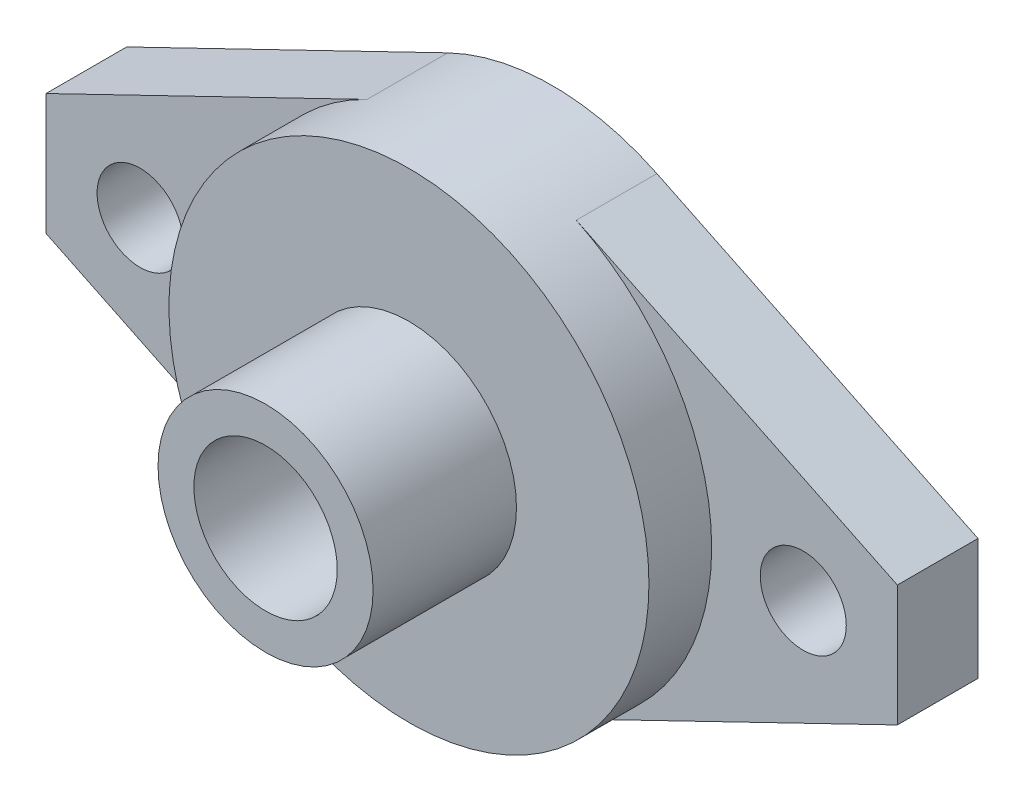
SolidWorks part; units mm, degrees
ref_plane "前视基准面" through (0, 0, 0) normal (0, 0, 1) x (1, 0, 0)
ref_plane "上视基准面" through (0, 0, 0) normal (0, 1, 0) x (1, 0, 0)
ref_plane "右视基准面" through (0, 0, 0) normal (1, 0, 0) x (0, 0, -1)
sketch "草图1" plane through (0, 0, 0) normal (0, 0, 1) x (1, 0, 0)
  line L0 (23.75, -3.3807) -> (23.75, 3.3807)
  line L1 (0, -13.3911) -> (0, -13.25) construction
  line L2 (-23.75, -3.3807) -> (-23.75, 3.3807)
  line L3 (23.75, 3.3807) -> (5.8347, 12.0531)
  line L4 (-23.75, 3.3807) -> (-5.8347, 12.0531)
  line L5 (-23.75, -3.3807) -> (-5.6321, -12.1512)
  line L6 (23.75, -3.3807) -> (5.6321, -12.1512)
  line L8 (0, 13.25) -> (0, 13.3911) construction
  circle A0 centre (0, 0) radius 4
  circle A1 centre (0, 0) radius 13.3911
  circle A2 centre (0, 0) radius 6
  circle A3 centre (0, 0) radius 13.25
  circle A4 centre (18.5, 0) radius 2.4
  circle A5 centre (-18.5, 0) radius 2.4
  point P6 (23.75, 0)
  point P7 (18.5, 0)
  point P19 (23.75, 0)
  dimension "D1" = 23.75
  dimension "D3" = 26.5
  dimension "D4" = 4.8
  dimension "D5" = 12
  dimension "D2" = 18.5
extrude "凸台-拉伸1" add sketch "草图1" along normal blind 4.5 contours A1 | A1 L6 L0 L3 A4 region at (14.6615, -7.4466, 0) region at (-14.6615, -7.4466, 0)
extrude "凸台-拉伸2" add sketch "草图1<3>" along normal blind 8 contours A1 A3 | L1 A3 A2 region at (0, -13.3532, 0) region at (-12.8752, 0, 0)
sketch "草图1<3>" plane through (0, 0, 0) normal (0, 0, 1) x (1, 0, 0) same geometry as "草图1"
extrude "凸台-拉伸3" add sketch "草图1<4>" along normal blind 16 separate body contours A2 A0 region at (-5.8303, 0, 0)
sketch "草图1<4>" plane through (0, 0, 0) normal (0, 0, 1) x (1, 0, 0) same geometry as "草图1"
